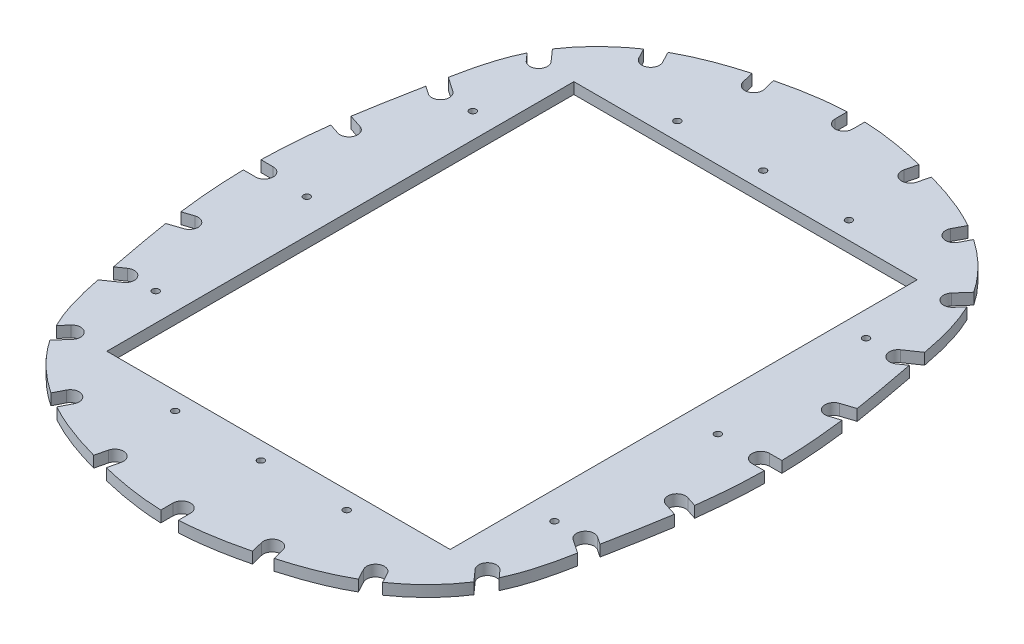
SolidWorks part; units mm, degrees
ref_plane "Front Plane" through (0, 0, 0) normal (0, 0, 1) x (1, 0, 0)
ref_plane "Top Plane" through (0, 0, 0) normal (0, 1, 0) x (1, 0, 0)
ref_plane "Right Plane" through (0, 0, 0) normal (1, 0, 0) x (0, 0, -1)
sketch "MainControlPoints" plane through (0, 0, 0) normal (0, 1, 0) x (1, 0, 0)
  line L1 (0, 188.5) -> (0, 0) construction
  line L2 (-44.5, 181.8105) -> (44.5, 181.8105) construction
  line L9 (-141, 0) -> (141, 0) construction
  line L10 (-86.25, 165.0195) -> (86.25, 165.0195) construction
  line L11 (-117.5, 132.6399) -> (117.5, 132.6399) construction
  line L12 (-130, 89.4108) -> (130, 89.4108) construction
  line L13 (-137.75, 45.0832) -> (137.75, 45.0832) construction
  spline S0 degree 3 poles (-44.8235, 182.8439) (0, 191.3281) (44.8235, 182.8439) (87.706, 168.1591) (121.8523, 134.6364) (129.8847, 89.1344) (138.6218, 45.2258) (142.1917, 0) (138.6218, -45.2258) (129.8847, -89.1344) (121.8523, -134.6364) (87.706, -168.1591) (44.8235, -182.8439) (0, -191.3281) (-44.8235, -182.8439) (-87.706, -168.1591) (-121.8523, -134.6364) (-129.8847, -89.1344) (-138.6218, -45.2258) (-142.1917, 0) (-138.6218, 45.2258) (-129.8847, 89.1344) (-121.8523, 134.6364) (-87.706, 168.1591) (-44.8235, 182.8439) (0, 191.3281) (44.8235, 182.8439) knots -0.124907 -0.083272 -0.041636 0 0.041636 0.083272 0.124907 0.166543 0.208179 0.25 0.291821 0.333457 0.375093 0.416728 0.458364 0.5 0.541636 0.583272 0.624907 0.666543 0.708179 0.75 0.791821 0.833457 0.875093 0.916728 0.958364 1 1.041636 1.083272 1.124907 only from (0, 188.5) to (0, 188.5)
  point P4 (0, 181.8105)
  point P7 (0, 0)
  point P8 (141, 0)
  point P9 (-141, 0)
  point P11 (44.5, 181.8105)
  point P14 (86.25, 165.0195)
  point P15 (0, 165.0195)
  point P16 (117.5, 132.6399)
  point P17 (130, 89.4108)
  point P18 (-44.5, 181.8105)
  point P19 (-86.25, 165.0195)
  point P20 (-117.5, 132.6399)
  point P23 (0, 132.6399)
  point P24 (137.75, 45.0832)
  point P25 (-130, 89.4108)
  point P26 (-137.75, 45.0832)
  point P27 (0, 188.5)
  point P30 (0, 89.4108)
  point P33 (0, 45.0832)
  point P34 (137.75, -45.0832)
  point P35 (130, -89.4108)
  point P36 (117.5, -132.6399)
  point P37 (86.25, -165.0195)
  point P38 (44.5, -181.8105)
  point P39 (0, -188.5)
  point P40 (-44.5, -181.8105)
  point P41 (-86.25, -165.0195)
  point P42 (-117.5, -132.6399)
  point P43 (-130, -89.4108)
  point P44 (-137.75, -45.0832)
  dimension "D3" = 282
  dimension "D2" = 188.5
  dimension "D5" = 45
  dimension "D6" = 45
  dimension "D1" = 89
  dimension "D4" = 172.5
  dimension "D7" = 45
  dimension "D8" = 235
  dimension "D9" = 45
  dimension "D10" = 260
  dimension "D11" = 45
  dimension "D12" = 275.5
ref_axis "Axis1" through (0, 0, -188.5) along (0, 1, 0)
ref_axis "Axis2" through (44.5, 0, -181.8105) along (0, 1, 0)
ref_axis "Axis3" through (86.25, 0, -165.0195) along (0, 1, 0)
ref_axis "Axis4" through (117.5, 0, -132.6399) along (0, 1, 0)
ref_axis "Axis5" through (130, 0, -89.4108) along (0, 1, 0)
ref_axis "Axis6" through (137.75, 0, -45.0832) along (0, 1, 0)
ref_axis "Axis7" through (141, 0, 0) along (0, 1, 0)
ref_axis "Axis8" through (137.75, 0, 45.0832) along (0, 1, 0)
ref_axis "Axis9" through (130, 0, 89.4108) along (0, 1, 0)
ref_axis "Axis10" through (117.5, 0, 132.6399) along (0, 1, 0)
ref_axis "Axis11" through (86.25, 0, 165.0195) along (0, 1, 0)
ref_axis "Axis12" through (44.5, 0, 181.8105) along (0, 1, 0)
ref_axis "Axis13" through (0, 0, 188.5) along (0, 1, 0)
ref_axis "Axis14" through (-44.5, 0, 181.8105) along (0, 1, 0)
ref_axis "Axis15" through (-86.25, 0, 165.0195) along (0, 1, 0)
ref_axis "Axis16" through (-117.5, 0, 132.6399) along (0, 1, 0)
ref_axis "Axis17" through (-130, 0, 89.4108) along (0, 1, 0)
ref_axis "Axis18" through (-137.75, 0, 45.0832) along (0, 1, 0)
ref_axis "Axis19" through (-141, 0, 0) along (0, 1, 0)
ref_axis "Axis20" through (-137.75, 0, -45.0832) along (0, 1, 0)
ref_axis "Axis21" through (-130, 0, -89.4108) along (0, 1, 0)
ref_axis "Axis22" through (-117.5, 0, -132.6399) along (0, 1, 0)
ref_axis "Axis23" through (-86.25, 0, -165.0195) along (0, 1, 0)
ref_axis "Axis24" through (-44.5, 0, -181.8105) along (0, 1, 0)
sketch "Sketch3" plane through (0, 0, 0) normal (0, 1, 0) x (1, 0, 0)
  spline S2 degree 3 poles (44.8235, 182.8439) (0, 191.3281) (-44.8235, 182.8439) (-87.706, 168.1591) (-121.8523, 134.6364) (-129.8847, 89.1344) (-138.6218, 45.2258) (-142.1917, 0) (-138.6218, -45.2258) (-129.8847, -89.1344) (-121.8523, -134.6364) (-87.706, -168.1591) (-44.8235, -182.8439) (0, -191.3281) (44.8235, -182.8439) (87.706, -168.1591) (121.8523, -134.6364) (129.8847, -89.1344) (138.6218, -45.2258) (142.1917, 0) (138.6218, 45.2258) (129.8847, 89.1344) (121.8523, 134.6364) (87.706, 168.1591) (44.8235, 182.8439) (0, 191.3281) (-44.8235, 182.8439) knots -0.124907 -0.083272 -0.041636 0 0.041636 0.083272 0.124907 0.166543 0.208179 0.25 0.291821 0.333457 0.375093 0.416728 0.458364 0.5 0.541636 0.583272 0.624907 0.666543 0.708179 0.75 0.791821 0.833457 0.875093 0.916728 0.958364 1 1.041636 1.083272 1.124907 only from (0, 188.5) to (0, 188.5)
  spline S3 degree 3 poles (44.8235, 182.8439) (0, 191.3281) (-44.8235, 182.8439) (-87.706, 168.1591) (-121.8523, 134.6364) (-129.8847, 89.1344) (-138.6218, 45.2258) (-142.1917, 0) (-138.6218, -45.2258) (-129.8847, -89.1344) (-121.8523, -134.6364) (-87.706, -168.1591) (-44.8235, -182.8439) (0, -191.3281) (44.8235, -182.8439) (87.706, -168.1591) (121.8523, -134.6364) (129.8847, -89.1344) (138.6218, -45.2258) (142.1917, 0) (138.6218, 45.2258) (129.8847, 89.1344) (121.8523, 134.6364) (87.706, 168.1591) (44.8235, 182.8439) (0, 191.3281) (-44.8235, 182.8439) knots -0.124907 -0.083272 -0.041636 0 0.041636 0.083272 0.124907 0.166543 0.208179 0.25 0.291821 0.333457 0.375093 0.416728 0.458364 0.5 0.541636 0.583272 0.624907 0.666543 0.708179 0.75 0.791821 0.833457 0.875093 0.916728 0.958364 1 1.041636 1.083272 1.124907 only from (0, 188.5) to (0, 188.5)
  dimension "D1" = 0
extrude "MainBody" add sketch "Sketch3" along normal blind 6.35
sketch "Sketch13" plane through (0, 6.35, 0) normal (0, 1, 0) x (1, 0, 0)
  spline S2 degree 3 poles (-0.0923, -195.5) (5.9061, -195.5) (11.7392, -195.085) (23.2981, -193.6453) (29.0237, -192.6199) (37.5559, -190.7615) (40.3905, -190.0886) (46.0447, -188.657) (48.8649, -187.9023) (53.0829, -186.6998) (54.4867, -186.2866) (57.2893, -185.4316) (58.6882, -184.9896) (62.8604, -183.6197) (65.6138, -182.6462) (73.7714, -179.5048) (79.0728, -177.1157) (86.7462, -172.933) (89.2575, -171.4385) (92.9463, -169.029) (94.1653, -168.1965) (96.5575, -166.4889) (97.7326, -165.6128) (101.1944, -162.9177) (103.4182, -161.032) (107.6923, -157.0772) (109.7427, -155.0081) (112.678, -151.7562) (113.633, -150.6474) (115.0284, -148.9451) (115.4873, -148.3711) (116.3925, -147.2097) (116.8393, -146.6213) (119.0306, -143.6582) (120.6466, -141.2209) (123.5916, -136.206) (124.9153, -133.6259) (127.2923, -128.3337) (128.3485, -125.623) (129.7723, -121.4785) (130.2202, -120.084) (131.0691, -117.272) (131.4694, -115.8571) (132.6042, -111.6095) (133.2755, -108.7656) (134.5145, -103.0626) (135.0819, -100.2036) (136.1775, -94.48) (136.707, -91.6156) (138.3251, -83.0265) (139.4215, -77.303) (141.5293, -65.8438) (142.5403, -60.108) (143.9035, -51.4821) (144.3323, -48.6031) (145.1247, -42.8358) (145.4885, -39.9475) (147.1362, -25.4811) (147.9101, -13.8294) (148.003, -0.6092) (148.0024, 0.8623) (147.9792, 3.8019) (147.9568, 5.2701) (147.8578, 9.6699) (147.7498, 12.5969) (147.3068, 21.3604) (146.8533, 27.1792) (145.6651, 38.7754) (144.9284, 44.5524) (143.2126, 56.0705) (142.2389, 61.8124) (140.1775, 73.2794) (139.0901, 79.0044) (137.4645, 87.5929) (136.9262, 90.4562) (135.8531, 96.1835) (135.3122, 99.0464) (133.5786, 107.6189) (132.2779, 113.3124) (130.1353, 120.3529) (129.6824, 121.7514) (128.7233, 124.5187) (128.2169, 125.8886) (126.6073, 129.9525) (125.4138, 132.6004) (122.7385, 137.7496) (121.2544, 140.2496) (118.8215, 143.8945) (117.9761, 145.0919) (116.2177, 147.4523) (115.3033, 148.6168) (112.4942, 152.0199) (110.5242, 154.1827) (106.4077, 158.3162) (104.2612, 160.2869) (99.8013, 164.0465) (97.4878, 165.8355) (93.8939, 168.384) (92.6724, 169.2128) (90.2027, 170.8151) (88.9554, 171.5879) (82.6598, 175.3171) (77.4348, 177.8708) (66.7035, 182.3362) (61.1969, 184.2476) (54.1978, 186.3725) (52.791, 186.7846) (49.9736, 187.5842) (48.5634, 187.9716) (44.3294, 189.1029) (41.5021, 189.818) (33.0032, 191.8167) (27.3144, 192.953) (15.8708, 194.6608) (10.1162, 195.2328) (1.4182, 195.5241) (-1.4925, 195.5238) (-7.3372, 195.3237) (-10.2708, 195.1267) (-14.6866, 194.6996) (-16.1609, 194.5352) (-19.0943, 194.1679) (-20.556, 193.9647) (-24.9277, 193.3015) (-27.824, 192.7881) (-36.4681, 191.071) (-42.1715, 189.6926) (-53.5026, 186.6371) (-59.1262, 184.9441) (-66.0624, 182.4605) (-67.445, 181.9454) (-70.1997, 180.8739) (-71.5737, 180.3168) (-75.6639, 178.5832) (-78.3432, 177.3468) (-83.5935, 174.6901) (-86.1644, 173.2698) (-91.1858, 170.2243) (-93.6357, 168.5985) (-97.2169, 166.0005) (-98.395, 165.108) (-100.7189, 163.2682) (-101.8655, 162.32) (-105.2234, 159.4186) (-107.3637, 157.4004) (-111.4418, 153.191) (-113.3796, 150.9998) (-117.0378, 146.4319) (-118.7583, 144.0551) (-121.1568, 140.3344) (-121.9259, 139.0681) (-123.0304, 137.1268) (-123.3898, 136.4736) (-124.087, 135.1618) (-124.4255, 134.5022) (-126.0692, 131.1868) (-127.2294, 128.4785) (-130.3408, 120.2205) (-131.9223, 114.5371) (-134.5909, 102.9918) (-135.6643, 97.1921) (-137.8355, 85.5987) (-138.9477, 79.8043) (-141.1029, 68.2094) (-142.1451, 62.4088) (-143.5618, 53.6948) (-144.0097, 50.788) (-144.8419, 44.9686) (-145.2255, 42.056) (-146.97, 27.4776) (-147.815, 15.7657) (-148.0521, -1.8942) (-147.9538, -7.7967) (-147.4225, -19.6316) (-146.9909, -25.5639) (-146.1143, -34.4827) (-145.7838, -37.4592) (-145.0527, -43.3941) (-144.6515, -46.3556) (-143.3516, -55.2244) (-142.36, -61.1163) (-140.253, -72.8796) (-139.1381, -78.7512) (-137.4708, -87.5593) (-136.9189, -90.496) (-135.8181, -96.3698) (-135.2627, -99.3053) (-133.4794, -108.0788) (-132.1352, -113.8842) (-129.4893, -122.4151) (-128.5024, -125.2292) (-126.8117, -129.3912) (-126.2131, -130.7686) (-125.2553, -132.818) (-124.9263, -133.498) (-124.2516, -134.843) (-123.9056, -135.5092) (-122.1306, -138.8075) (-120.5688, -141.343) (-117.1925, -146.2303) (-115.378, -148.582) (-111.5149, -153.1153) (-109.4647, -155.2983) (-105.1449, -159.494) (-102.9036, -161.4797) (-95.9543, -167.1259) (-91.0211, -170.4758) (-84.4967, -174.1698) (-83.1716, -174.8856) (-80.5028, -176.2632) (-79.1594, -176.925) (-75.1047, -178.8358) (-72.3686, -180.0105) (-64.0786, -183.2871) (-58.4429, -185.1422) (-49.8888, -187.6214) (-47.0211, -188.3984) (-41.2605, -189.8765) (-38.3664, -190.5739) (-32.5429, -191.862) (-29.6099, -192.4531) (-23.735, -193.4975) (-20.7901, -193.9515) (-14.8831, -194.699) (-11.9208, -194.9924) (-7.4624, -195.2928) (-5.9738, -195.3696) (-3.7367, -195.4473) (-2.6172, -195.4768) (-1.3092, -195.4942) (-0.6548, -195.4985) (-0.3742, -195.4995) (-0.1871, -195.4999) (-0.0923, -195.5) (5.9061, -195.5) (11.7392, -195.085) knots -0.000244 -0.000244 0 0 0.015625 0.015625 0.03125 0.03125 0.039063 0.039063 0.046875 0.046875 0.050781 0.050781 0.054688 0.054688 0.0625 0.0625 0.078125 0.078125 0.085938 0.085938 0.089844 0.089844 0.09375 0.09375 0.101563 0.101563 0.109375 0.109375 0.113281 0.113281 0.115234 0.115234 0.117188 0.117188 0.125 0.125 0.132813 0.132813 0.140625 0.140625 0.144531 0.144531 0.148438 0.148438 0.15625 0.15625 0.164063 0.164063 0.171875 0.171875 0.1875 0.1875 0.203125 0.203125 0.210938 0.210938 0.21875 0.21875 0.25 0.25 0.253906 0.253906 0.257813 0.257813 0.265625 0.265625 0.28125 0.28125 0.296875 0.296875 0.3125 0.3125 0.328125 0.328125 0.335938 0.335938 0.34375 0.34375 0.359375 0.359375 0.363281 0.363281 0.367188 0.367188 0.375 0.375 0.382813 0.382813 0.386719 0.386719 0.390625 0.390625 0.398438 0.398438 0.40625 0.40625 0.414063 0.414063 0.417969 0.417969 0.421875 0.421875 0.4375 0.4375 0.453125 0.453125 0.457031 0.457031 0.460938 0.460938 0.46875 0.46875 0.484375 0.484375 0.5 0.5 0.507813 0.507813 0.515625 0.515625 0.519531 0.519531 0.523438 0.523438 0.53125 0.53125 0.546875 0.546875 0.5625 0.5625 0.566406 0.566406 0.570313 0.570313 0.578125 0.578125 0.585938 0.585938 0.59375 0.59375 0.597656 0.597656 0.601563 0.601563 0.609375 0.609375 0.617188 0.617188 0.625 0.625 0.628906 0.628906 0.630859 0.630859 0.632813 0.632813 0.640625 0.640625 0.65625 0.65625 0.671875 0.671875 0.6875 0.6875 0.703125 0.703125 0.710937 0.710937 0.71875 0.71875 0.75 0.75 0.765625 0.765625 0.78125 0.78125 0.789062 0.789062 0.796875 0.796875 0.8125 0.8125 0.828125 0.828125 0.835937 0.835937 0.84375 0.84375 0.859375 0.859375 0.867187 0.867187 0.871094 0.871094 0.873047 0.873047 0.875 0.875 0.882812 0.882812 0.890625 0.890625 0.898437 0.898437 0.90625 0.90625 0.921875 0.921875 0.925781 0.925781 0.929687 0.929687 0.9375 0.9375 0.953125 0.953125 0.960937 0.960937 0.96875 0.96875 0.976562 0.976562 0.984375 0.984375 0.992188 0.992188 0.996094 0.996094 0.998047 0.999023 0.999512 0.999756 0.999756 1 1 1.015625 1.015625 1.03125 only from (0, -195.5) to (0, -195.5)
  spline S3 degree 3 poles (-0.0923, -195.5) (5.9061, -195.5) (11.7392, -195.085) (23.2981, -193.6453) (29.0237, -192.6199) (37.5559, -190.7615) (40.3905, -190.0886) (46.0447, -188.657) (48.8649, -187.9023) (53.0829, -186.6998) (54.4867, -186.2866) (57.2893, -185.4316) (58.6882, -184.9896) (62.8604, -183.6197) (65.6138, -182.6462) (73.7714, -179.5048) (79.0728, -177.1157) (86.7462, -172.933) (89.2575, -171.4385) (92.9463, -169.029) (94.1653, -168.1965) (96.5575, -166.4889) (97.7326, -165.6128) (101.1944, -162.9177) (103.4182, -161.032) (107.6923, -157.0772) (109.7427, -155.0081) (112.678, -151.7562) (113.633, -150.6474) (115.0284, -148.9451) (115.4873, -148.3711) (116.3925, -147.2097) (116.8393, -146.6213) (119.0306, -143.6582) (120.6466, -141.2209) (123.5916, -136.206) (124.9153, -133.6259) (127.2923, -128.3337) (128.3485, -125.623) (129.7723, -121.4785) (130.2202, -120.084) (131.0691, -117.272) (131.4694, -115.8571) (132.6042, -111.6095) (133.2755, -108.7656) (134.5145, -103.0626) (135.0819, -100.2036) (136.1775, -94.48) (136.707, -91.6156) (138.3251, -83.0265) (139.4215, -77.303) (141.5293, -65.8438) (142.5403, -60.108) (143.9035, -51.4821) (144.3323, -48.6031) (145.1247, -42.8358) (145.4885, -39.9475) (147.1362, -25.4811) (147.9101, -13.8294) (148.003, -0.6092) (148.0024, 0.8623) (147.9792, 3.8019) (147.9568, 5.2701) (147.8578, 9.6699) (147.7498, 12.5969) (147.3068, 21.3604) (146.8533, 27.1792) (145.6651, 38.7754) (144.9284, 44.5524) (143.2126, 56.0705) (142.2389, 61.8124) (140.1775, 73.2794) (139.0901, 79.0044) (137.4645, 87.5929) (136.9262, 90.4562) (135.8531, 96.1835) (135.3122, 99.0464) (133.5786, 107.6189) (132.2779, 113.3124) (130.1353, 120.3529) (129.6824, 121.7514) (128.7233, 124.5187) (128.2169, 125.8886) (126.6073, 129.9525) (125.4138, 132.6004) (122.7385, 137.7496) (121.2544, 140.2496) (118.8215, 143.8945) (117.9761, 145.0919) (116.2177, 147.4523) (115.3033, 148.6168) (112.4942, 152.0199) (110.5242, 154.1827) (106.4077, 158.3162) (104.2612, 160.2869) (99.8013, 164.0465) (97.4878, 165.8355) (93.8939, 168.384) (92.6724, 169.2128) (90.2027, 170.8151) (88.9554, 171.5879) (82.6598, 175.3171) (77.4348, 177.8708) (66.7035, 182.3362) (61.1969, 184.2476) (54.1978, 186.3725) (52.791, 186.7846) (49.9736, 187.5842) (48.5634, 187.9716) (44.3294, 189.1029) (41.5021, 189.818) (33.0032, 191.8167) (27.3144, 192.953) (15.8708, 194.6608) (10.1162, 195.2328) (1.4182, 195.5241) (-1.4925, 195.5238) (-7.3372, 195.3237) (-10.2708, 195.1267) (-14.6866, 194.6996) (-16.1609, 194.5352) (-19.0943, 194.1679) (-20.556, 193.9647) (-24.9277, 193.3015) (-27.824, 192.7881) (-36.4681, 191.071) (-42.1715, 189.6926) (-53.5026, 186.6371) (-59.1262, 184.9441) (-66.0624, 182.4605) (-67.445, 181.9454) (-70.1997, 180.8739) (-71.5737, 180.3168) (-75.6639, 178.5832) (-78.3432, 177.3468) (-83.5935, 174.6901) (-86.1644, 173.2698) (-91.1858, 170.2243) (-93.6357, 168.5985) (-97.2169, 166.0005) (-98.395, 165.108) (-100.7189, 163.2682) (-101.8655, 162.32) (-105.2234, 159.4186) (-107.3637, 157.4004) (-111.4418, 153.191) (-113.3796, 150.9998) (-117.0378, 146.4319) (-118.7583, 144.0551) (-121.1568, 140.3344) (-121.9259, 139.0681) (-123.0304, 137.1268) (-123.3898, 136.4736) (-124.087, 135.1618) (-124.4255, 134.5022) (-126.0692, 131.1868) (-127.2294, 128.4785) (-130.3408, 120.2205) (-131.9223, 114.5371) (-134.5909, 102.9918) (-135.6643, 97.1921) (-137.8355, 85.5987) (-138.9477, 79.8043) (-141.1029, 68.2094) (-142.1451, 62.4088) (-143.5618, 53.6948) (-144.0097, 50.788) (-144.8419, 44.9686) (-145.2255, 42.056) (-146.97, 27.4776) (-147.815, 15.7657) (-148.0521, -1.8942) (-147.9538, -7.7967) (-147.4225, -19.6316) (-146.9909, -25.5639) (-146.1143, -34.4827) (-145.7838, -37.4592) (-145.0527, -43.3941) (-144.6515, -46.3556) (-143.3516, -55.2244) (-142.36, -61.1163) (-140.253, -72.8796) (-139.1381, -78.7512) (-137.4708, -87.5593) (-136.9189, -90.496) (-135.8181, -96.3698) (-135.2627, -99.3053) (-133.4794, -108.0788) (-132.1352, -113.8842) (-129.4893, -122.4151) (-128.5024, -125.2292) (-126.8117, -129.3912) (-126.2131, -130.7686) (-125.2553, -132.818) (-124.9263, -133.498) (-124.2516, -134.843) (-123.9056, -135.5092) (-122.1306, -138.8075) (-120.5688, -141.343) (-117.1925, -146.2303) (-115.378, -148.582) (-111.5149, -153.1153) (-109.4647, -155.2983) (-105.1449, -159.494) (-102.9036, -161.4797) (-95.9543, -167.1259) (-91.0211, -170.4758) (-84.4967, -174.1698) (-83.1716, -174.8856) (-80.5028, -176.2632) (-79.1594, -176.925) (-75.1047, -178.8358) (-72.3686, -180.0105) (-64.0786, -183.2871) (-58.4429, -185.1422) (-49.8888, -187.6214) (-47.0211, -188.3984) (-41.2605, -189.8765) (-38.3664, -190.5739) (-32.5429, -191.862) (-29.6099, -192.4531) (-23.735, -193.4975) (-20.7901, -193.9515) (-14.8831, -194.699) (-11.9208, -194.9924) (-7.4624, -195.2928) (-5.9738, -195.3696) (-3.7367, -195.4473) (-2.6172, -195.4768) (-1.3092, -195.4942) (-0.6548, -195.4985) (-0.3742, -195.4995) (-0.1871, -195.4999) (-0.0923, -195.5) (5.9061, -195.5) (11.7392, -195.085) knots -0.000244 -0.000244 0 0 0.015625 0.015625 0.03125 0.03125 0.039063 0.039063 0.046875 0.046875 0.050781 0.050781 0.054688 0.054688 0.0625 0.0625 0.078125 0.078125 0.085938 0.085938 0.089844 0.089844 0.09375 0.09375 0.101563 0.101563 0.109375 0.109375 0.113281 0.113281 0.115234 0.115234 0.117188 0.117188 0.125 0.125 0.132813 0.132813 0.140625 0.140625 0.144531 0.144531 0.148438 0.148438 0.15625 0.15625 0.164063 0.164063 0.171875 0.171875 0.1875 0.1875 0.203125 0.203125 0.210938 0.210938 0.21875 0.21875 0.25 0.25 0.253906 0.253906 0.257813 0.257813 0.265625 0.265625 0.28125 0.28125 0.296875 0.296875 0.3125 0.3125 0.328125 0.328125 0.335938 0.335938 0.34375 0.34375 0.359375 0.359375 0.363281 0.363281 0.367188 0.367188 0.375 0.375 0.382813 0.382813 0.386719 0.386719 0.390625 0.390625 0.398438 0.398438 0.40625 0.40625 0.414063 0.414063 0.417969 0.417969 0.421875 0.421875 0.4375 0.4375 0.453125 0.453125 0.457031 0.457031 0.460938 0.460938 0.46875 0.46875 0.484375 0.484375 0.5 0.5 0.507813 0.507813 0.515625 0.515625 0.519531 0.519531 0.523438 0.523438 0.53125 0.53125 0.546875 0.546875 0.5625 0.5625 0.566406 0.566406 0.570313 0.570313 0.578125 0.578125 0.585938 0.585938 0.59375 0.59375 0.597656 0.597656 0.601563 0.601563 0.609375 0.609375 0.617188 0.617188 0.625 0.625 0.628906 0.628906 0.630859 0.630859 0.632813 0.632813 0.640625 0.640625 0.65625 0.65625 0.671875 0.671875 0.6875 0.6875 0.703125 0.703125 0.710937 0.710937 0.71875 0.71875 0.75 0.75 0.765625 0.765625 0.78125 0.78125 0.789062 0.789062 0.796875 0.796875 0.8125 0.8125 0.828125 0.828125 0.835937 0.835937 0.84375 0.84375 0.859375 0.859375 0.867187 0.867187 0.871094 0.871094 0.873047 0.873047 0.875 0.875 0.882812 0.882812 0.890625 0.890625 0.898437 0.898437 0.90625 0.90625 0.921875 0.921875 0.925781 0.925781 0.929687 0.929687 0.9375 0.9375 0.953125 0.953125 0.960937 0.960937 0.96875 0.96875 0.976562 0.976562 0.984375 0.984375 0.992188 0.992188 0.996094 0.996094 0.998047 0.999023 0.999512 0.999756 0.999756 1 1 1.015625 1.015625 1.03125 only from (0, -195.5) to (0, -195.5)
  dimension "D1" = 7
extrude "Extrude2Lip" add sketch "Sketch13" against normal up to surface (6.35 mm away)
sketch "Sketch14" plane through (0, 6.35, 0) normal (0, 1, 0) x (1, 0, 0)
  line L0 (-5, 188.5) -> (-5, 199.1798)
  line L1 (-5, 199.1798) -> (5, 199.1798)
  line L2 (5, 199.1798) -> (5, 188.5)
  line L9 (0, 188.5) -> (0, 199.1798) construction
  line L13 (-5, 188.5) -> (5, 188.5) construction
  line L20 (39.6434, 182.9992) -> (42.1824, 193.3728)
  line L21 (42.1824, 193.3728) -> (51.8957, 190.9953)
  line L22 (0, 0) -> (44.5, 181.8105) construction
  line L23 (0, 0) -> (86.25, 165.0195) construction
  line L24 (0, 0) -> (117.5, 132.6399) construction
  line L25 (0, 0) -> (130, 89.4108) construction
  line L26 (0, 0) -> (137.75, 45.0832) construction
  line L27 (0, 0) -> (141, 0.3435) construction
  line L28 (0, 0) -> (0, 188.5) construction
  line L29 (51.8957, 190.9953) -> (49.3566, 180.6217)
  line L30 (44.5, 181.8105) -> (47.039, 192.1841) construction
  line L31 (39.6434, 182.9992) -> (49.3566, 180.6217) construction
  line L32 (81.8188, 167.3355) -> (86.7658, 176.8005)
  line L33 (86.7658, 176.8005) -> (95.6283, 172.1684)
  line L34 (95.6283, 172.1684) -> (90.6812, 162.7034)
  line L35 (86.25, 165.0195) -> (91.197, 174.4844) construction
  line L36 (81.8188, 167.3355) -> (90.6812, 162.7034) construction
  line L37 (113.7573, 135.9554) -> (125.8891, 149.6503)
  line L38 (125.8891, 149.6503) -> (133.3744, 143.0193)
  line L39 (133.3744, 143.0193) -> (121.2427, 129.3244)
  line L40 (117.5, 132.6399) -> (129.6317, 146.3348) construction
  line L41 (113.7573, 135.9554) -> (121.2427, 129.3244) construction
  line L42 (127.1666, 93.5305) -> (142.2527, 103.9064)
  line L43 (142.2527, 103.9064) -> (147.9195, 95.667)
  line L44 (147.9195, 95.667) -> (132.8334, 85.2912)
  line L45 (130, 89.4108) -> (145.0861, 99.7867) construction
  line L46 (127.1666, 93.5305) -> (132.8334, 85.2912) construction
  line L47 (136.1948, 49.8352) -> (153.5963, 55.5304)
  line L48 (153.5963, 55.5304) -> (156.7067, 46.0265)
  line L49 (156.7067, 46.0265) -> (139.3052, 40.3312)
  line L50 (137.75, 45.0832) -> (155.1515, 50.7784) construction
  line L51 (136.1948, 49.8352) -> (139.3052, 40.3312) construction
  line L52 (140.9878, 5.3435) -> (159.2975, 5.3881)
  line L53 (159.2975, 5.3881) -> (159.3219, -4.6119)
  line L54 (159.3219, -4.6119) -> (141.0122, -4.6565)
  line L55 (141, 0.3435) -> (159.3097, 0.3881) construction
  line L56 (140.9878, 5.3435) -> (141.0122, -4.6565) construction
  line L57 (-140.9878, 5.3435) -> (-141.0122, -4.6565) construction
  line L58 (-141, 0.3435) -> (-159.3097, 0.3881) construction
  line L59 (-136.1948, 49.8352) -> (-139.3052, 40.3312) construction
  line L60 (-137.75, 45.0832) -> (-155.1515, 50.7784) construction
  line L61 (-127.1666, 93.5305) -> (-132.8334, 85.2912) construction
  line L62 (-130, 89.4108) -> (-145.0861, 99.7867) construction
  line L63 (-113.7573, 135.9554) -> (-121.2427, 129.3244) construction
  line L64 (-117.5, 132.6399) -> (-129.6317, 146.3348) construction
  line L65 (-81.8188, 167.3355) -> (-90.6812, 162.7034) construction
  line L66 (-86.25, 165.0195) -> (-91.197, 174.4844) construction
  line L67 (-39.6434, 182.9992) -> (-49.3566, 180.6217) construction
  line L68 (-44.5, 181.8105) -> (-47.039, 192.1841) construction
  line L69 (-159.3219, -4.6119) -> (-141.0122, -4.6565)
  line L70 (-159.2975, 5.3881) -> (-159.3219, -4.6119)
  line L71 (-140.9878, 5.3435) -> (-159.2975, 5.3881)
  line L72 (-156.7067, 46.0265) -> (-139.3052, 40.3312)
  line L73 (-153.5963, 55.5304) -> (-156.7067, 46.0265)
  line L74 (-136.1948, 49.8352) -> (-153.5963, 55.5304)
  line L75 (-147.9195, 95.667) -> (-132.8334, 85.2912)
  line L76 (-142.2527, 103.9064) -> (-147.9195, 95.667)
  line L77 (-127.1666, 93.5305) -> (-142.2527, 103.9064)
  line L78 (-133.3744, 143.0193) -> (-121.2427, 129.3244)
  line L79 (-125.8891, 149.6503) -> (-133.3744, 143.0193)
  line L80 (-113.7573, 135.9554) -> (-125.8891, 149.6503)
  line L81 (-95.6283, 172.1684) -> (-90.6812, 162.7034)
  line L82 (-86.7658, 176.8005) -> (-95.6283, 172.1684)
  line L83 (-81.8188, 167.3355) -> (-86.7658, 176.8005)
  line L84 (-51.8957, 190.9953) -> (-49.3566, 180.6217)
  line L85 (-42.1824, 193.3728) -> (-51.8957, 190.9953)
  line L86 (-39.6434, 182.9992) -> (-42.1824, 193.3728)
  line L87 (-43.6136, -182.0251) -> (-46.1021, -192.411) construction
  line L88 (-38.7512, -183.1902) -> (-48.476, -180.8601) construction
  line L89 (-85.4449, -165.4378) -> (-90.3457, -174.9267) construction
  line L90 (-81.0024, -167.7322) -> (-89.8874, -163.1433) construction
  line L91 (-116.8523, -133.2108) -> (-128.9172, -146.9647) construction
  line L92 (-113.0935, -136.508) -> (-120.6111, -129.9136) construction
  line L93 (-129.5628, -90.0432) -> (-144.5981, -100.4924) construction
  line L94 (-126.7093, -94.149) -> (-132.4163, -85.9374) construction
  line L95 (-137.5287, -45.7539) -> (-154.9022, -51.5338) construction
  line L96 (-135.9503, -50.4982) -> (-139.1071, -41.0095) construction
  line L97 (136.436, -49.171) -> (139.5001, -39.652) construction
  line L98 (137.968, -44.4115) -> (155.3971, -50.0219) construction
  line L99 (127.6208, -92.9098) -> (133.2474, -84.6429) construction
  line L100 (130.4341, -88.7763) -> (145.5706, -99.0786) construction
  line L101 (114.4184, -135.3995) -> (121.8714, -128.7321) construction
  line L102 (118.1449, -132.0658) -> (130.3432, -145.7014) construction
  line L103 (82.6331, -166.9349) -> (91.4729, -162.2596) construction
  line L104 (87.053, -164.5972) -> (92.0461, -174.038) construction
  line L105 (40.5346, -182.8038) -> (50.2361, -180.3791) construction
  line L106 (45.3853, -181.5915) -> (47.9749, -191.9526) construction
  line L107 (-4.0815, -188.5221) -> (5.9184, -188.4734) construction
  line L108 (0.9185, -188.4978) -> (0.9705, -199.1775) construction
  line L109 (-38.7512, -183.1902) -> (-41.2397, -193.576)
  line L110 (-41.2397, -193.576) -> (-50.9644, -191.2459)
  line L111 (-50.9644, -191.2459) -> (-48.476, -180.8601)
  line L112 (-81.0024, -167.7322) -> (-85.9033, -177.2212)
  line L113 (-85.9033, -177.2212) -> (-94.7882, -172.6323)
  line L114 (-94.7882, -172.6323) -> (-89.8874, -163.1433)
  line L115 (-113.0935, -136.508) -> (-125.1584, -150.2619)
  line L116 (-125.1584, -150.2619) -> (-132.676, -143.6675)
  line L117 (-132.676, -143.6675) -> (-120.6111, -129.9136)
  line L118 (-126.7093, -94.149) -> (-141.7447, -104.5983)
  line L119 (-141.7447, -104.5983) -> (-147.4516, -96.3866)
  line L120 (-147.4516, -96.3866) -> (-132.4163, -85.9374)
  line L121 (-135.9503, -50.4982) -> (-153.3239, -56.2781)
  line L122 (-153.3239, -56.2781) -> (-156.4806, -46.7895)
  line L123 (-156.4806, -46.7895) -> (-139.1071, -41.0095)
  line L124 (156.9292, -45.2624) -> (139.5001, -39.652)
  line L125 (153.865, -54.7813) -> (156.9292, -45.2624)
  line L126 (136.436, -49.171) -> (153.865, -54.7813)
  line L127 (148.3839, -94.9451) -> (133.2474, -84.6429)
  line L128 (142.7573, -103.212) -> (148.3839, -94.9451)
  line L129 (127.6208, -92.9098) -> (142.7573, -103.212)
  line L130 (134.0697, -142.3677) -> (121.8714, -128.7321)
  line L131 (126.6167, -149.0351) -> (134.0697, -142.3677)
  line L132 (114.4184, -135.3995) -> (126.6167, -149.0351)
  line L133 (96.466, -171.7004) -> (91.4729, -162.2596)
  line L134 (87.6262, -176.3756) -> (96.466, -171.7004)
  line L135 (82.6331, -166.9349) -> (87.6262, -176.3756)
  line L136 (52.8257, -190.7402) -> (50.2361, -180.3791)
  line L137 (43.1241, -193.1649) -> (52.8257, -190.7402)
  line L138 (40.5346, -182.8038) -> (43.1241, -193.1649)
  line L139 (5.9704, -199.1531) -> (5.9184, -188.4734)
  line L140 (-4.0294, -199.2018) -> (5.9704, -199.1531)
  line L141 (-4.0815, -188.5221) -> (-4.0294, -199.2018)
  arc A0 (-5, 188.5) -> (5, 188.5) centre (0, 188.5) ccw
  arc A1 (39.6434, 182.9992) -> (49.3566, 180.6217) centre (44.5, 181.8105) ccw
  arc A2 (81.8188, 167.3355) -> (90.6812, 162.7034) centre (86.25, 165.0195) ccw
  arc A3 (113.7573, 135.9554) -> (121.2427, 129.3244) centre (117.5, 132.6399) ccw
  arc A4 (127.1666, 93.5305) -> (132.8334, 85.2912) centre (130, 89.4108) ccw
  arc A5 (136.1948, 49.8352) -> (139.3052, 40.3312) centre (137.75, 45.0832) ccw
  arc A6 (140.9878, 5.3435) -> (141.0122, -4.6565) centre (141, 0.3435) ccw
  arc A7 (-140.9878, 5.3435) -> (-141.0122, -4.6565) centre (-141, 0.3435) cw
  arc A8 (-136.1948, 49.8352) -> (-139.3052, 40.3312) centre (-137.75, 45.0832) cw
  arc A9 (-127.1666, 93.5305) -> (-132.8334, 85.2912) centre (-130, 89.4108) cw
  arc A10 (-113.7573, 135.9554) -> (-121.2427, 129.3244) centre (-117.5, 132.6399) cw
  arc A11 (-81.8188, 167.3355) -> (-90.6812, 162.7034) centre (-86.25, 165.0195) cw
  arc A12 (-39.6434, 182.9992) -> (-49.3566, 180.6217) centre (-44.5, 181.8105) cw
  arc A13 (-38.7512, -183.1902) -> (-48.476, -180.8601) centre (-43.6136, -182.0251) ccw
  arc A14 (-81.0024, -167.7322) -> (-89.8874, -163.1433) centre (-85.4449, -165.4378) ccw
  arc A15 (-113.0935, -136.508) -> (-120.6111, -129.9136) centre (-116.8523, -133.2108) ccw
  arc A16 (-126.7093, -94.149) -> (-132.4163, -85.9374) centre (-129.5628, -90.0432) ccw
  arc A17 (-135.9503, -50.4982) -> (-139.1071, -41.0095) centre (-137.5287, -45.7539) ccw
  arc A18 (136.436, -49.171) -> (139.5001, -39.652) centre (137.968, -44.4115) cw
  arc A19 (127.6208, -92.9098) -> (133.2474, -84.6429) centre (130.4341, -88.7763) cw
  arc A20 (114.4184, -135.3995) -> (121.8714, -128.7321) centre (118.1449, -132.0658) cw
  arc A21 (82.6331, -166.9349) -> (91.4729, -162.2596) centre (87.053, -164.5972) cw
  arc A22 (40.5346, -182.8038) -> (50.2361, -180.3791) centre (45.3853, -181.5915) cw
  arc A23 (-4.0815, -188.5221) -> (5.9184, -188.4734) centre (0.9185, -188.4978) cw
  point P16 (44.5, 181.8105)
  dimension "D1" = 5
  dimension "D4" = 10
extrude "Slots" cut sketch "Sketch14" against normal up to next
ref_plane "MajorAxisPlane" through (0, 0, 0) normal (-1, 0, 0) x (0, 0, 1)
ref_plane "MinorAxisPlane" through (0, 0, 0) normal (0, 0, 1) x (1, 0, 0)
sketch "Sketch16" plane through (0, 6.35, 0) normal (0, 1, 0) x (1, 0, 0)
  line L1 (-97.5, -132.6399) -> (97.5, -132.6399)
  line L2 (-97.5, -132.6399) -> (-97.5, 132.6399)
  line L3 (-97.5, 132.6399) -> (97.5, 132.6399)
  line L4 (97.5, -132.6399) -> (97.5, 132.6399)
  line L5 (-97.5, -132.6399) -> (97.5, 132.6399) construction
  line L6 (-97.5, 132.6399) -> (97.5, -132.6399) construction
  line L7 (-117.5, 132.6399) -> (117.5, 132.6399) construction
  point P0 (0, 0)
  dimension "D1" = 20
extrude "OuterRidge" cut sketch "Sketch16" against normal through all
hole_wizard "#6 Clearance Hole1" positions "Sketch17" profile "Sketch18" hole size "#6" standard "ANSI Inch" end condition through all
sketch "Sketch17" plane through (0, 6.35, 0) normal (0, 1, 0) x (1, 0, 0)
  line L0 (0, 188.5) -> (0, 0) construction
  line L1 (-117.5, 132.6399) -> (117.5, 132.6399) construction
  line L2 (-97.5, 142.6399) -> (0, 142.6399) construction
  line L5 (0, 142.6399) -> (0, 132.4272) construction
  line L7 (-3.5008, 0) -> (3.5008, 0) construction
  line L8 (-130, 89.4108) -> (130, 89.4108) construction
  line L12 (-125.8803, 86.5774) -> (-97.5, 86.5774) construction
  line L13 (-97.5, 132.6399) -> (-97.5, -132.6399) construction
  line L18 (-136, 0.3313) -> (-97.5, 0) construction
  line L20 (0, 0) -> (0, -89.1534) construction
  arc A0 (-132.8334, 85.2912) -> (-127.1666, 93.5305) centre (-130, 89.4108) ccw construction
  arc A2 (-141.0122, -4.6565) -> (-140.9878, 5.3435) centre (-141, 0.3435) ccw construction
  point P16 (-48.75, 142.6399)
  point P33 (0, 142.6399)
  point P42 (-48.75, 142.6399)
  point P51 (48.75, -142.6399)
  point P52 (0, -142.6399)
  point P53 (-48.75, -142.6399)
  point P54 (-111.6902, 89.4108)
  point P56 (-116.75, 0.1657)
  point P83 (-111.6902, 86.5774)
  point P101 (-116.75, 0.1657)
  point P103 (-113.2269, -89.1534)
  point P109 (0, 0)
  point P110 (0, 0)
  point P111 (0, 0)
  point P112 (0, 0)
  point P113 (0, 0)
  point P114 (113.2269, -89.1534)
  point P115 (116.75, 0.1657)
  point P116 (111.6902, 89.4108)
  point P117 (48.75, 142.6399)
  dimension "D1" = 10
sketch "Sketch18" plane through (-48.75, 6.35, -142.6399) normal (1, 0, 0) x (0, 0, 1)
  line L0 (0, 0) -> (0, 6.35)
  line L1 (0, 6.35) -> (1.8986, 6.35)
  line L2 (1.8986, 6.35) -> (1.8986, 0)
  line L5 (1.8986, 0) -> (0, 0)
  line L11 (0, -6.35) -> (0, 107.95) construction
  dimension "Thru Hole Dia." = 3.7973
  dimension "Thru Hole Depth" = 6.35
equation "\"MajorAxis\"= 377mm"
equation "\"MinorAxis\"= 282mm"
equation "\"MajorDiagonal\"= 353mm"
equation "\"SlotSpacing\"= 45mm"
equation "\"SlotRadius\"=5"
equation "\"D3@MainControlPoints\" = \"MinorAxis\""
equation "\"D2@MainControlPoints\" = \"MajorAxis\" / 2"
equation "\"D5@MainControlPoints\" = \"SlotSpacing\""
equation "\"D7@MainControlPoints\" = \"SlotSpacing\""
equation "\"D9@MainControlPoints\" = \"SlotSpacing\""
equation "\"D11@MainControlPoints\" = \"SlotSpacing\""
equation "\"D1@Sketch14\"=\"SlotRadius\""
equation "\"D4@Sketch14\"=\"SlotRadius\" * 2"
equation "\"Pt2LipEdge\"=7"
equation "\"D1@Sketch13\"=\"Pt2LipEdge\""
equation "\"OuterRidgeWidth\"=113.618"
